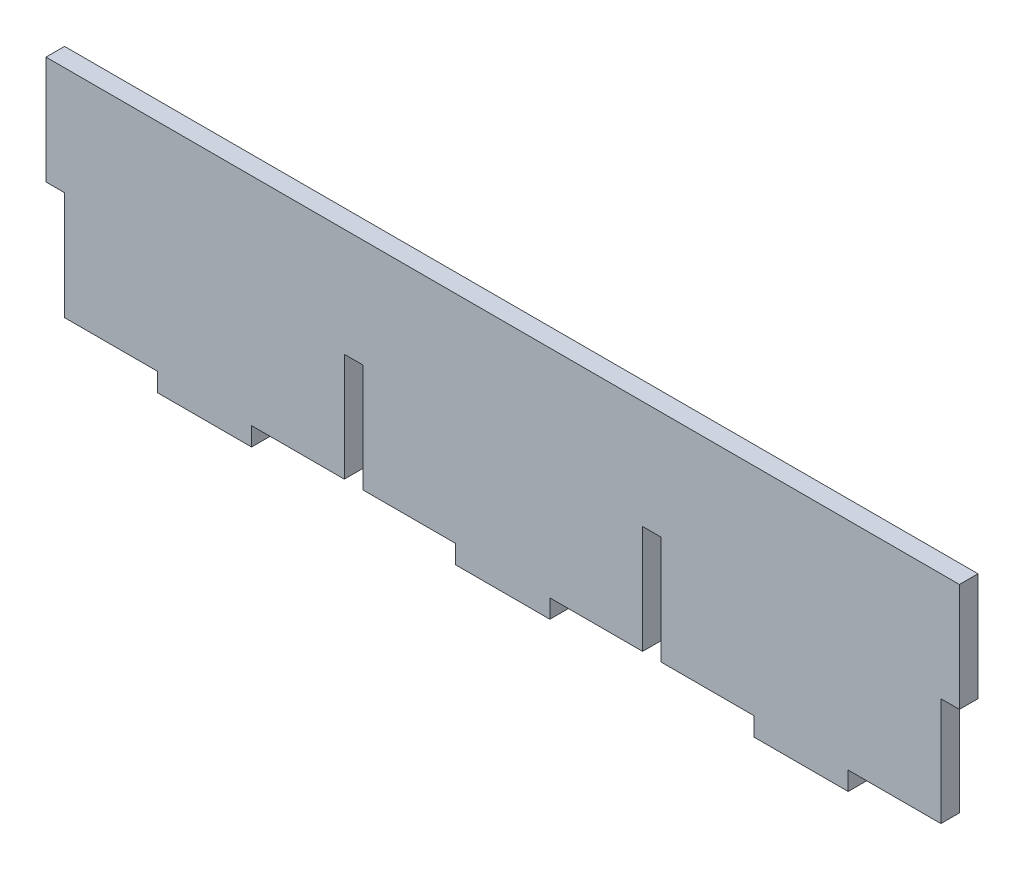
SolidWorks part; units mm, degrees
ref_plane "Front Plane" through (0, 0, 0) normal (0, 0, 1) x (1, 0, 0)
ref_plane "Top Plane" through (0, 0, 0) normal (0, 1, 0) x (1, 0, 0)
ref_plane "Right Plane" through (0, 0, 0) normal (1, 0, 0) x (0, 0, -1)
sketch "Sketch1" plane through (0, 0, 0) normal (0, 0, 1) x (1, 0, 0)
  line L0 (73.875, 1.5) -> (70.875, 1.5)
  line L1 (-73.875, -19) -> (73.875, -19)
  line L2 (-73.875, -19) -> (-73.875, 19)
  line L3 (-73.875, 19) -> (73.875, 19)
  line L4 (73.875, -19) -> (73.875, 19)
  line L5 (-73.875, -19) -> (73.875, 19) construction
  line L6 (-73.875, 19) -> (73.875, -19) construction
  line L7 (70.875, 1.5) -> (70.875, -19)
  line L8 (70.875, -19) -> (25.625, -19)
  line L9 (25.625, -19) -> (25.625, 1.5)
  line L10 (25.625, 1.5) -> (22.625, 1.5)
  line L11 (22.625, 1.5) -> (22.625, -19)
  line L12 (22.625, -19) -> (-22.625, -19)
  line L13 (-22.625, -19) -> (-22.625, 1.5)
  line L14 (-22.625, 1.5) -> (-25.625, 1.5)
  line L15 (-25.625, 1.5) -> (-25.625, -19)
  line L16 (-73.875, 1.5) -> (-70.875, 1.5)
  line L17 (-70.875, 1.5) -> (-70.875, -19)
  line L18 (-25.625, -16) -> (-40.625, -16)
  line L19 (-40.625, -16) -> (-40.625, -19)
  line L20 (-40.625, -19) -> (-55.875, -19)
  line L21 (-55.875, -19) -> (-55.875, -16)
  line L22 (-55.875, -16) -> (-70.875, -16)
  line L23 (-22.625, -16) -> (-7.625, -16)
  line L24 (-7.625, -16) -> (-7.625, -19)
  line L25 (-7.625, -19) -> (7.625, -19)
  line L26 (7.625, -19) -> (7.625, -16)
  line L27 (7.625, -16) -> (22.625, -16)
  line L28 (25.625, -16) -> (40.625, -16)
  line L29 (40.625, -16) -> (40.625, -19)
  line L30 (70.875, -16) -> (55.875, -16)
  line L31 (55.875, -16) -> (55.875, -19)
  point P0 (0, 0)
  dimension "D1" = 38
  dimension "D2" = 147.75
  dimension "D3" = 3
  dimension "D4" = 45.25
  dimension "D5" = 3
  dimension "D6" = 45.25
  dimension "D7" = 3
  dimension "D8" = 3
  dimension "D9" = 15
  dimension "D10" = 15
  dimension "D11" = 3
  dimension "D12" = 3
  dimension "D13" = 15
  dimension "D14" = 15
  dimension "D15" = 15
  dimension "D16" = 15
  dimension "D17" = 17.5
  dimension "D18" = 17.5
  dimension "D19" = 3
  dimension "D20" = 15.25
extrude "Boss-Extrude1" add sketch "Sketch1" along normal blind 3 contours L16 L17 L1 L15 L14 L13 L11 L10 L9 L7 L0 L4 L3 L2 region at (0, 1.3489, 0)
